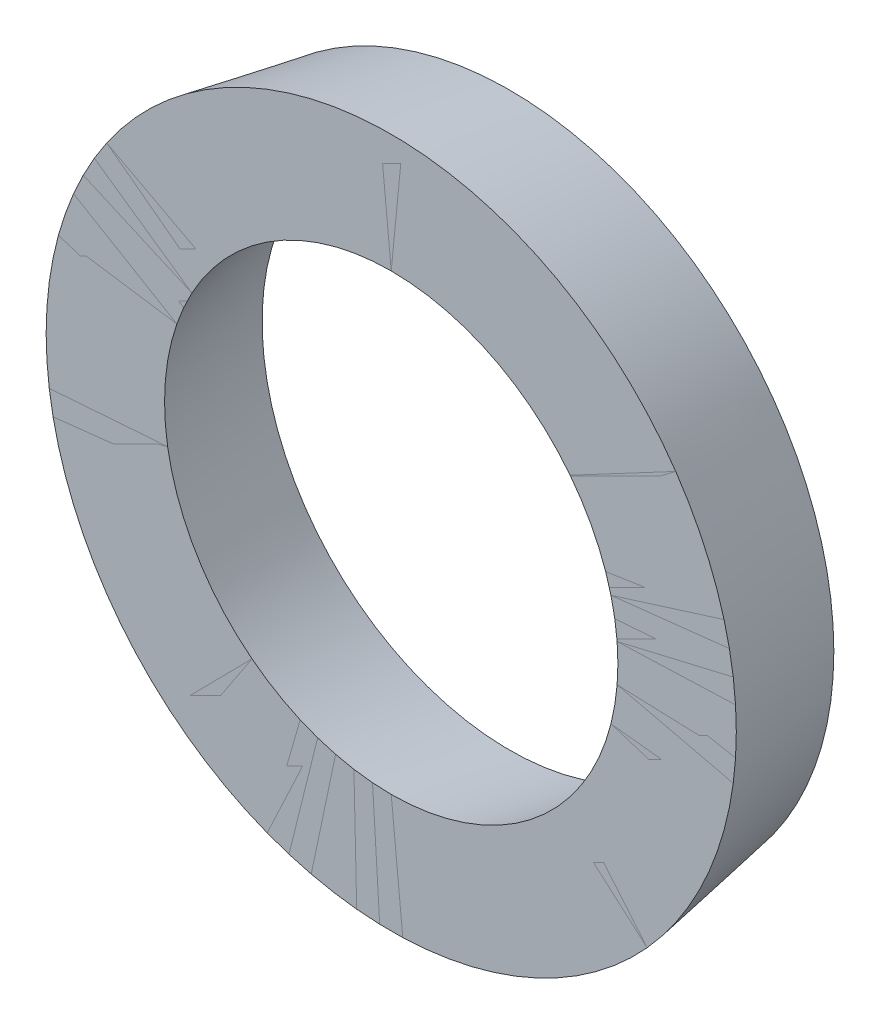
SolidWorks part; units mm, degrees
note: The reader was unsure of these and kept them because the rebuilt part matched: shared geometry of "Эскиз1<3>".
ref_plane "Спереди" through (0, 0, 0) normal (0, 0, 1) x (1, 0, 0)
ref_plane "Сверху" through (0, 0, 0) normal (0, 1, 0) x (1, 0, 0)
ref_plane "Справа" through (0, 0, 0) normal (1, 0, 0) x (0, 0, -1)
sketch "Эскиз1" plane through (0, 0, 0) normal (0, 0, 1) x (1, 0, 0)
  circle A0 centre (0, 0) radius 29.1429
  circle A1 centre (0, 0) radius 19.1429
  dimension "D1" = 10
surface "Поверхность-Заполнить1" sketch "Эскиз1"
extrude "Бобышка-Вытянуть1" add sketch "Эскиз1<3>" against normal blind 10 draft 10
sketch "Эскиз1<3>" plane through (0, 0, 0) normal (0, 0, 1) x (1, 0, 0) same geometry as "Эскиз1"
